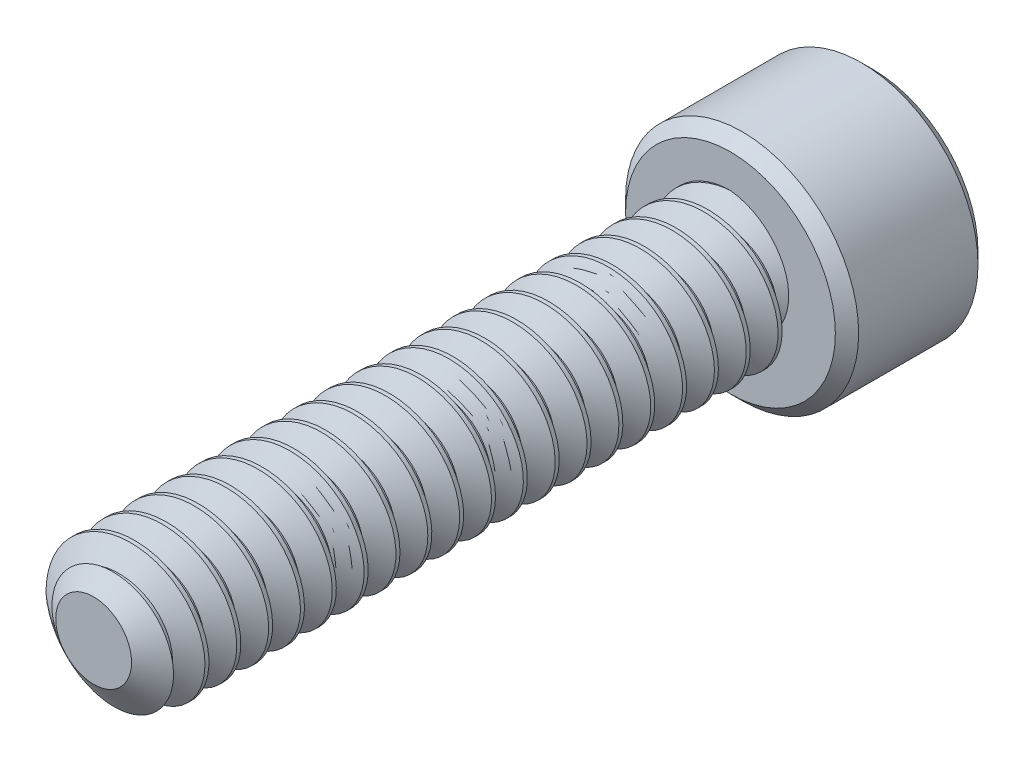
SolidWorks part; units mm, degrees
ref_plane "Front Plane" through (0, 0, 0) normal (0, 0, 1) x (1, 0, 0)
ref_plane "Top Plane" through (0, 0, 0) normal (0, 1, 0) x (1, 0, 0)
ref_plane "Right Plane" through (0, 0, 0) normal (1, 0, 0) x (0, 0, -1)
sketch "Sketch1" plane through (0, 0, 0) normal (0, 0, 1) x (1, 0, 0)
  circle A0 centre (0, 0) radius 1.4224
  dimension "OD" = 2.8448
extrude "Extrude1" add sketch "Sketch1" against normal blind 12.7
sketch "Sketch2" plane through (0, 0, 0) normal (0, 0, 1) x (1, 0, 0)
  circle A0 centre (0, 0) radius 1.4224 construction
  circle A1 centre (0, 0) radius 1.4224
curve "Helix/Spiral1" pitch 0.635 height 13.335 radius 1.4224 centre (0, 0, 0) axis (0, 0, -1) start towards (0, 1, 0) parameters "pitch"=0.635
sketch "Sketch3" plane through (0, 0, 0) normal (1, 0, 0) x (0, 0, -1)
  line L0 (-0.5556, 1.4224) -> (-0.3175, 1.01)
  line L1 (-0.3175, 1.01) -> (-0.2381, 1.01)
  line L2 (-0.2381, 1.01) -> (0, 1.4224)
  line L3 (-0.5556, 1.4224) -> (0, 1.4224)
  line L4 (-0.2778, 1.4224) -> (-0.2778, 1.01) construction
  line L5 (-0.4366, 1.2162) -> (-0.1191, 1.2162) construction
  line L6 (0, 1.4224) -> (0, -1.4224) construction
  dimension "D1" = 0.0794
  dimension "D2" = 0.3175
  dimension "D3" = 60
sweep "Cut-Sweep1" cut profiles "Sketch3" path "Helix/Spiral1"
sketch "Sketch4" plane through (0, 0, 0) normal (1, 0, 0) x (0, 0, -1)
  line L0 (0.4666, 1.4224) -> (0, 0.756)
  line L1 (0, 0.756) -> (0, 1.4224)
  line L2 (0.4666, 1.4224) -> (0, 1.4224)
  line L3 (-0.5556, 1.4224) -> (0, 1.4224) construction
  line L4 (0, 0) -> (7.0209, 0) construction
  dimension "D1" = 55
  dimension "D2" = 0.254
revolve "Cut-Revolve1" cut sketch "Sketch4" angle 360 about L4
sketch "Sketch5" plane through (0, 0, 0) normal (1, 0, 0) x (0, 0, -1)
  line L0 (12.7, -1.0232) -> (12.7, 1.0149) construction
  line L1 (12.7, 1.5494) -> (87.4327, 1.5494)
  line L2 (12.7, 1.5494) -> (12.7, 0)
  line L3 (12.7, 0) -> (87.3125, 0)
  line L4 (87.3125, 1.2192) -> (87.3125, 0)
  line L5 (87.4327, 1.5494) -> (87.3125, 1.2192)
  line L6 (0, 0) -> (9.9695, 0) construction
  point P3 (87.3125, 1.5494)
  point P10 (87.3125, 1.5494)
  dimension "D1" = 0.3302
  dimension "Thread min" = 87.3125
  dimension "D2" = 0.127
  dimension "D3" = 20
revolve "partially thread" [suppressed] add sketch "Sketch5" angle 360 about L6
sketch "Sketch6" plane through (0, 0, -12.7) normal (0, 0, -1) x (-1, 0, 0)
  circle A0 centre (0, 0) radius 2.3241
  dimension "head dia" = 4.6482
extrude "Extrude2" add sketch "Sketch6" along normal blind 2.8448
sketch "Sketch7" plane through (0, 0, -15.5448) normal (0, 0, -1) x (-1, 0, 0)
  line L1 (0, 1.3748) -> (-1.1906, 0.6874)
  line L2 (-1.1906, 0.6874) -> (-1.1906, -0.6874)
  line L3 (-1.1906, -0.6874) -> (0, -1.3748)
  line L4 (0, -1.3748) -> (1.1906, -0.6874)
  line L5 (1.1906, -0.6874) -> (1.1906, 0.6874)
  line L6 (1.1906, 0.6874) -> (0, 1.3748)
  circle A0 centre (0, 0) radius 1.1906 construction
  dimension "hex dia" = 2.3813
extrude "Cut-Extrude1" cut sketch "Sketch7" against normal blind 1.7859
sketch "Sketch8" plane through (0, 0, -15.5448) normal (0, 0, -1) x (-1, 0, 0)
  circle A0 centre (0, 0) radius 1.3748
extrude "Cut-Extrude2" cut sketch "Sketch8" against normal through all draft 45
chamfer "Chamfer1" distance 0.2324 angle 45 2 edges at (-2.3241, 0, -15.5448) (-2.3241, 0, -12.7)
sketch "Sketch9" plane through (0, 0, 0) normal (1, 0, 0) x (0, 0, -1)
  line L0 (0, 1.4224) -> (0, -1.4224) construction
  line L1 (6.6675, 1.4224) -> (6.6675, -1.4224) construction
  dimension "D1" = 6.6675
equation "\"D3@Helix/Spiral1\" = \"screw length@Extrude1\"+\"pitch@Helix/Spiral1\""
equation "\"D1@Sketch3\" = \"pitch@Helix/Spiral1\"*.125"
equation "\"D2@Sketch3\" = \"pitch@Helix/Spiral1\"*.5"
equation "\"D1@Cut-Extrude1\" = \"hex dia@Sketch7\"*.75"
equation "\"D1@Chamfer1\" = \"head dia@Sketch6\"*.05"
equation "\"D1@Sketch9\" = \"pitch@Helix/Spiral1\"*10.5"
